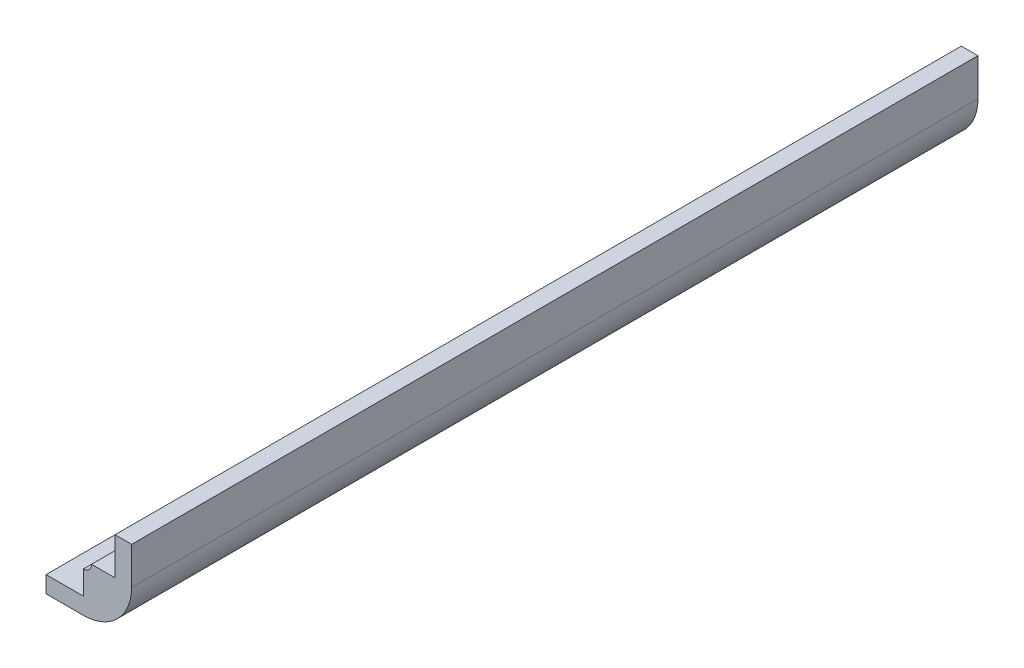
SolidWorks part; units mm, degrees
ref_plane "Front Plane" through (0, 0, 0) normal (0, 0, 1) x (1, 0, 0)
ref_plane "Top Plane" through (0, 0, 0) normal (0, 1, 0) x (1, 0, 0)
ref_plane "Right Plane" through (0, 0, 0) normal (1, 0, 0) x (0, 0, -1)
ref_axis "Axis1" through (0, 0, -88.99) along (0, 0, 1)
sketch "Sketch16" plane through (0, 0, 0) normal (0, 1, 0) x (1, 0, 0)
  line L0 (0, -50.8) -> (0, 50.8) construction
  point P2 (0, 0)
  dimension "D1" = 101.6
sketch "Sketch2" plane through (0, 0, 0) normal (0, 0, 1) x (1, 0, 0)
  line L0 (-7.3025, -1.5) -> (-2.54, -1.5) construction
  line L1 (-7.3025, -1.5) -> (-7.3025, 1.5) construction
  line L2 (-2.54, -1.5) -> (-2.54, 1.5) construction
  line L3 (-7.3025, 1.5) -> (-2.54, 1.5) construction
  line L4 (-2.54, 0) -> (0, 0) construction
  line L5 (0, 0) -> (0, 2.54) construction
  line L6 (1.5, 2.54) -> (-1.5, 2.54) construction
  line L7 (1.5, 2.54) -> (1.5, 7.3025) construction
  line L8 (-1.5, 2.54) -> (-1.5, 7.3025) construction
  line L9 (1.5, 7.3025) -> (-1.5, 7.3025) construction
  point P7 (0, 2.54)
  point P11 (-0.6532, 7.4263)
  point P16 (-1.5, 1.5)
  dimension "D1" = 3
  dimension "D2" = 4.7625
  dimension "D3" = 2.54
  dimension "D4" = 90
ref_plane "Plane1" through (0, 0, 0) normal (-1, 0, 0) x (0, 1, 0)
sketch "Sketch7" plane through (0, 0, 0) normal (0, 0, 1) x (1, 0, 0)
  line L0 (-7.3025, -1.5) -> (-2.54, -1.5)
  line L1 (-7.3025, -1.5) -> (-7.3025, -3.6212)
  line L2 (-2.54, -1.5) -> (-2.54, -3.6212)
  line L3 (-7.3025, -3.6212) -> (-2.54, -3.6212)
  dimension "D1" = 2.1212
extrude "Boss-Extrude2" add sketch "Sketch7" along normal mid plane 107.95 separate body
sketch "Sketch8" plane through (0, 0, 0) normal (0, 0, 1) x (1, 0, 0)
  line L0 (1.5, 2.54) -> (1.5, 7.3025)
  line L1 (1.5, 2.54) -> (3.6212, 2.54)
  line L2 (1.5, 7.3025) -> (3.6212, 7.3025)
  line L3 (3.6212, 2.54) -> (3.6212, 7.3025)
  line L4 (-2.54, -3.6212) -> (-2.54, -1.5) construction
extrude "Boss-Extrude3" add sketch "Sketch8" along normal mid plane 107.95
sketch "Sketch11" plane through (0, 0, 0) normal (0, 0, 1) x (1, 0, 0)
  line L1 (-2.54, -1.5) -> (-7.3025, -1.5)
  line L2 (-7.3025, -1.5) -> (-7.3025, -3.6212)
  line L8 (3.6212, 7.3025) -> (1.5, 7.3025)
  line L9 (1.5, 7.3025) -> (1.5, 2.54)
  line L13 (1.5, 2.54) -> (-1.5, 2.54)
  line L14 (-1.5, 2.54) -> (-1.5, 1.5) construction
  line L15 (-1.5, 1.5) -> (-2.54, 1.5) construction
  line L17 (-2.54, 1.5) -> (-2.54, -1.5)
  line L18 (3.6212, 7.3025) -> (3.6212, 2.54)
  line L19 (1.5, 2.54) -> (3.6212, 2.54) construction
  line L20 (-2.54, -3.6212) -> (-7.3025, -3.6212)
  arc A0 (-1.5, 2.54) -> (-2.54, 1.5) centre (-2.54, 2.54) cw
  arc A1 (3.6212, 2.54) -> (-2.54, -3.6212) centre (-2.54, 2.54) cw
  point P17 (0, 0)
extrude "Boss-Extrude4" add sketch "Sketch11" along normal mid plane 107.95
ref_plane "Midplane" through (0, 0, 0) normal (0.7071, 0.7071, 0) x (0.7071, -0.7071, 0)
equation "\"plate_thickness\"= 3mm"
equation "\"D1@Sketch2\"=\"plate_thickness\""
equation "\"joiner_lip_width\"= .1875"
equation "\"D2@Sketch2\"=\"joiner_lip_width\""
equation "\"face_gap\"=0.1"
equation "\"D3@Sketch2\"=\"face_gap\""
equation "\"inside_angle\"= 90"
equation "\"joiner_thickness\"= 0.0835128"
equation "\"edge_length\"= 4"
equation "\"Face1_TopLip\"= \"angle\" * 2"
equation "\"Face1_BottomLip\"= \"angle\" * 2"
equation "\"Face2_TopLip\"= 45deg"
equation "\"Face2_BottomLip\"= 45deg"
equation "\"D1@Sketch7\"=\"joiner_thickness\""
equation "\"D1@Boss-Extrude2\"=\"Extrude_to\""
equation "\"D1@Boss-Extrude3\"=\"Extrude_to\""
equation "\"D1@Boss-Extrude4\"=\"Extrude_to\""
equation "\"Extrude_to\"= \"edge_length\" + .25"
equation "\"D1@Sketch16\"=\"edge_length\""
equation "\"angle\"= atn ( 0.1 / ( ( 3.7085 - 3.0793 ) / 2 ) )"
equation "\"D2@Sketch5\"=\"Face2_TopLip\"/2"
equation "\"D1@Sketch5\"=\"Face2_BottomLip\"/2"
equation "\"D2@Sketch4\"=\"Face1_TopLip\"/2"
equation "\"D1@Sketch4\"=\"Face1_BottomLip\"/2"
equation "\"D1\" = \"edge_length\""
equation "\"D2@Sketch12\"=\"Face1_TopLip\"/2"
equation "\"D1@Sketch12\"=\"Face1_BottomLip\"/2"
